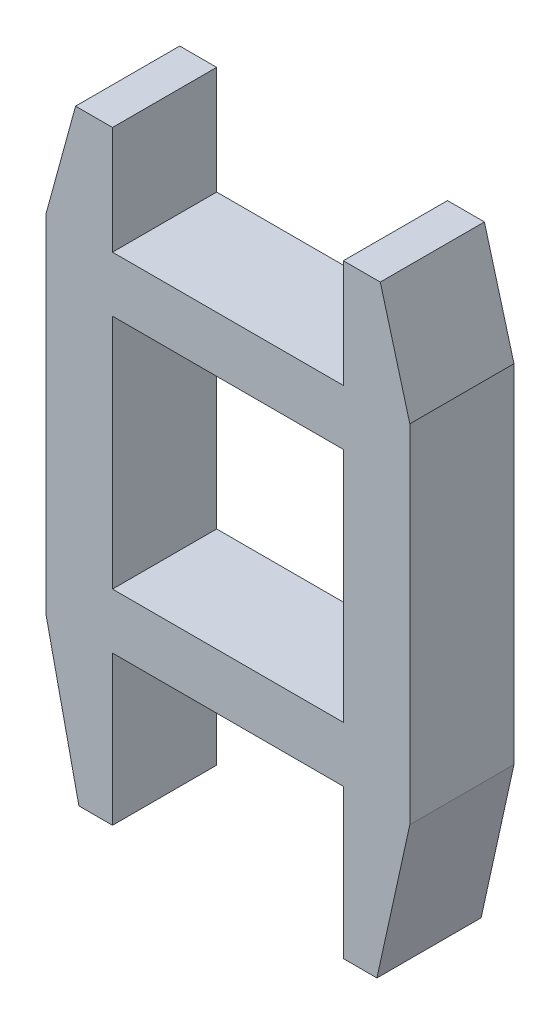
SolidWorks part; units mm, degrees
material "Acrylic (Medium-high impact)"
ref_plane "Front Plane" through (0, 0, 0) normal (0, 0, 1) x (1, 0, 0)
ref_plane "Top Plane" through (0, 0, 0) normal (0, 1, 0) x (1, 0, 0)
ref_plane "Right Plane" through (0, 0, 0) normal (1, 0, 0) x (0, 0, -1)
sketch "Sketch1" plane through (0, 0, 0) normal (0, 0, 1) x (1, 0, 0)
  line L0 (1247.1596, 962.2772) -> (1247.1596, 949.4772)
  line L1 (1263.2596, 947.9772) -> (1243.5596, 947.9772) construction
  line L2 (1247.1596, 946.4772) -> (1243.5596, 946.4772) construction
  line L3 (1247.1596, 962.2772) -> (1259.6596, 962.2772)
  line L4 (1245.1596, 971.1264) -> (1247.1596, 971.1264)
  line L5 (1247.1596, 971.1264) -> (1247.1596, 965.2772)
  line L6 (1247.1596, 955.8772) -> (1259.6596, 955.8772) construction
  line L7 (1259.6596, 965.2772) -> (1247.1596, 965.2772)
  line L8 (1243.5596, 965.2772) -> (1243.5596, 946.4772)
  line L9 (1243.5596, 946.4772) -> (1245.3404, 938.398)
  line L10 (1247.1596, 965.2772) -> (1243.5596, 965.2772) construction
  line L11 (1259.6596, 946.4772) -> (1247.1596, 946.4772)
  line L12 (1243.5596, 965.2772) -> (1245.1596, 971.1264)
  line L13 (1247.1596, 938.398) -> (1247.1596, 946.4772)
  line L14 (1245.3404, 938.398) -> (1247.1596, 938.398)
  line L15 (1247.1596, 949.4772) -> (1259.6596, 949.4772)
  line L16 (1259.6596, 965.2772) -> (1263.2596, 965.2772) construction
  line L17 (1259.6596, 946.4772) -> (1263.2596, 946.4772) construction
  line L18 (1261.4789, 938.398) -> (1259.6596, 938.398)
  line L19 (1253.4096, -39.6851) -> (1253.4096, 49960.3149) construction
  line L20 (1259.6596, 938.398) -> (1259.6596, 946.4772)
  line L21 (1263.2596, 965.2772) -> (1261.6596, 971.1264)
  line L22 (1263.2596, 946.4772) -> (1261.4789, 938.398)
  line L23 (1263.2596, 965.2772) -> (1263.2596, 946.4772)
  line L24 (1259.6596, 971.1264) -> (1259.6596, 965.2772)
  line L25 (1261.6596, 971.1264) -> (1259.6596, 971.1264)
  line L26 (1263.2596, 963.7772) -> (1243.5596, 963.7772) construction
  line L27 (1259.6596, 962.2772) -> (1259.6596, 949.4772)
  point P2 (1263.2596, 955.8772)
  point P14 (1243.5596, 955.8772)
  point P15 (1253.4096, 965.2772)
  point P20 (1253.4096, 963.7772)
  point P26 (1253.4096, 955.8772)
  point P28 (1253.4096, 965.2772)
  point P30 (1253.4096, 962.2772)
  point P31 (1253.4096, 947.9772)
  point P33 (1253.4096, 949.4772)
  point P36 (1253.4096, 946.4772)
  point P38 (1253.4096, 962.2772)
  dimension "D1" = 6.25
  dimension "D2" = 5.8492
  dimension "D3" = 2
  dimension "D4" = 3
  dimension "D5" = 9.4
  dimension "D6" = 8.0792
  dimension "D7" = 192.43
  dimension "D8" = 3.6
extrude "Boss-Extrude1" add sketch "Sketch1" along normal blind 5.64
